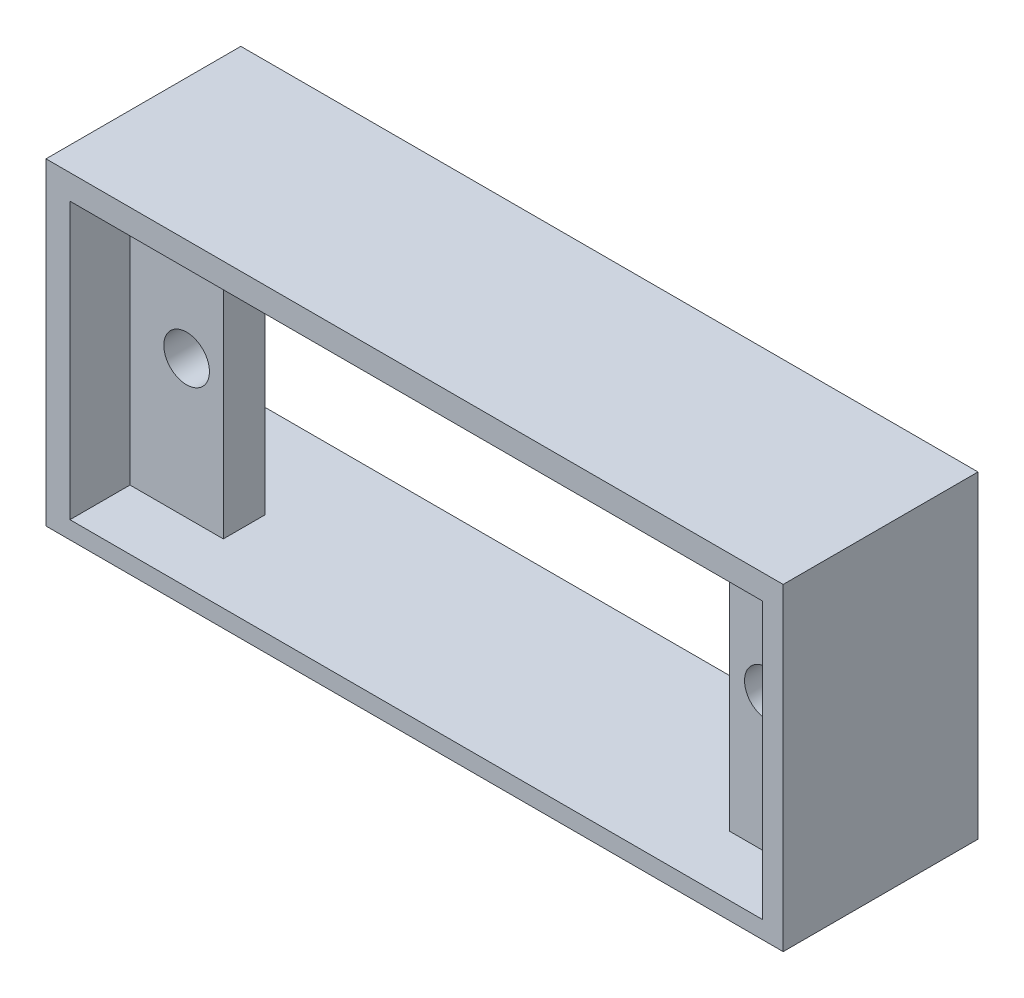
SolidWorks part; units mm, degrees
material "Custom Plastic"
ref_plane "Front Plane" through (0, 0, 0) normal (0, 0, 1) x (1, 0, 0)
ref_plane "Top Plane" through (0, 0, 0) normal (0, 1, 0) x (1, 0, 0)
ref_plane "Right Plane" through (0, 0, 0) normal (1, 0, 0) x (0, 0, -1)
sketch "Sketch1" plane through (0, 0, 0) normal (0, 0, 1) x (1, 0, 0)
  line L1 (0, 15) -> (145, 15)
  line L2 (0, 15) -> (0, -15)
  line L3 (0, -15) -> (145, -15)
  line L4 (145, 15) -> (145, -15)
  circle A0 centre (0, 0) radius 27.5
  circle A1 centre (145, 0) radius 27.5
  circle A2 centre (0, 0) radius 20
  point P9 (0, 0)
  dimension "D1" = 55
  dimension "D4" = 55
  dimension "D5" = 40
  dimension "D2" = 145
  dimension "D3" = 30
extrude "Boss-Extrude1" add sketch "Sketch1" along normal blind 25 contours L3 A1 L1 L4 | A1 L1 A0 L3 | L1 A1 L3 L4 | A2 L3 A0 L1 | A2 L1 A0 L3 | L3 A2 L1 L2 | L1 A2 L3 L2 region at (-6.7804, 0, 0) region at (9.0671, 0, 0) region at (-20.747, 0, 0) region at (21.8665, 0, 0) region at (72.5, 0, 0) region at (151.4116, 0, 0) region at (131.9332, 0, 0)
sketch "Sketch16" plane through (0, 0, 0) normal (0, 0, -1) x (-1, 0, 0)
  line L0 (-121.9511, -15) -> (-133.5193, -6.65) construction
  line L1 (-133.5193, -6.65) -> (-166.9193, -6.65)
  line L2 (-133.5193, -6.65) -> (-133.5193, 6.65)
  line L3 (-133.5193, 6.65) -> (-166.9193, 6.65)
  line L4 (-166.9193, -6.65) -> (-166.9193, 6.65)
  line L5 (-23.0489, -15) -> (-121.9511, -15) construction
  line L7 (-133.5193, 6.65) -> (-121.9511, 15) construction
  arc A1 (-121.9511, 15) -> (-121.9511, -15) centre (-145, 0) ccw construction
  dimension "D1" = 11.5682
  dimension "D2" = 33.4
  dimension "D3" = 13.3
extrude "Cut-Extrude10" cut sketch "Sketch16" against normal blind 4.5
ref_plane "Plane1" through (0, 0, 0) normal (0, -1, 0) x (-1, 0, 0)
sketch "Sketch19" plane through (0, 0, 0) normal (0, 0, -1) x (-1, 0, 0)
  circle A0 centre (0, 0) radius 20
extrude "Cut-Extrude14" cut sketch "Sketch19" against normal blind 5 contours A0
ref_plane "Plane2" through (0, 0, 6.5) normal (0, 0, -1) x (-1, 0, 0)
sketch "Sketch17" plane through (0, 0, 0) normal (0, 0, -1) x (-1, 0, 0)
  line L1 (-162.4193, 6.65) -> (-138.0193, 6.65)
  line L2 (-162.4193, 6.65) -> (-162.4193, -6.65)
  line L3 (-162.4193, -6.65) -> (-138.0193, -6.65)
  line L4 (-133.5193, -6.65) -> (-133.5193, 6.65)
  line L5 (-133.5193, 6.65) -> (-166.9193, 6.65)
  line L7 (-166.9193, -6.65) -> (-133.5193, -6.65)
  line L8 (-133.5193, -6.65) -> (-133.5193, 6.65)
  line L9 (-133.5193, 6.65) -> (-166.9193, 6.65)
  line L11 (-166.9193, -6.65) -> (-133.5193, -6.65)
  line L12 (-138.0193, 6.65) -> (-138.0193, -6.65)
  line L15 (-166.9193, 6.65) -> (-166.9193, -6.65)
  line L17 (-166.9193, 6.65) -> (-166.9193, -6.65)
  line M9 (-166.9193, 6.65) -> (-133.5193, 6.65)
  line M11 (-133.5193, -6.65) -> (-166.9193, -6.65)
  dimension "D2" = 4.5
  dimension "D3" = 4.5
  dimension "D1" = 0
extrude "Cut-Extrude11" cut sketch "Sketch17" against normal through all contours L12 L2 M9 M11 region at (150.2193, 0, 0)
sketch "Sketch18" plane through (0, 0, 0) normal (0, -1, 0) x (-1, 0, 0)
  line L0 (-138.0193, -25) -> (-138.0193, -15)
  line L6 (-122.0193, -25) -> (-122.0193, -22.5)
  line L8 (-166.9193, -4.5) -> (-162.4193, -4.5)
  line L9 (-166.9193, 0) -> (-166.9193, -4.5)
  line L11 (-166.9193, 0) -> (-166.9193, -4.5)
  line L13 (-133.5193, -4.5) -> (-133.5193, 0)
  line L14 (-133.5193, 0) -> (-166.9193, 0)
  line L16 (-166.9193, -4.5) -> (-162.4193, -4.5)
  line L21 (-133.5193, -4.5) -> (-133.5193, 0)
  line L22 (-133.5193, 0) -> (-166.9193, 0)
  line L26 (-122.0193, -22.5) -> (-138.0193, -15)
  line L28 (-23.0489, -25) -> (-121.9511, -25) construction
  line L30 (-138.0193, -25) -> (-122.0193, -25)
  line L31 (-138.0193, -15) -> (-138.0193, -25)
  line L34 (-162.4193, -25) -> (-138.0193, -25)
  line L35 (-162.4193, -25) -> (-138.0193, -25)
  line L36 (-138.0193, -25) -> (-138.0193, -4.5)
  line L37 (-138.0193, -25) -> (-138.0193, -4.5)
  line L38 (-162.4193, -4.5) -> (-162.4193, -25)
  line L40 (-162.4193, -4.5) -> (-162.4193, -25)
  line L42 (-138.0193, -4.5) -> (-133.5193, -4.5)
  line L43 (-138.0193, -4.5) -> (-133.5193, -4.5)
  dimension "D2" = 15
  dimension "D3" = 16
  dimension "D4" = 2.5
  dimension "D1" = 0
extrude "Cut-Extrude13" cut sketch "Sketch18" against normal mid plane 12.9 contours L0 region at (131.6193, 0, 21.5)
sketch "Sketch20" plane through (0, 0, 6.5) normal (0, 0, -1) x (-1, 0, 0)
  line L0 (-133.5193, 6.65) -> (-166.9193, 6.65) construction
  line L1 (-166.9193, 6.65) -> (-133.5193, 6.65)
  line L2 (-166.9193, 6.65) -> (-166.9193, -6.65)
  line L3 (-166.9193, -6.65) -> (-133.5193, -6.65)
  line L4 (-133.5193, 6.65) -> (-133.5193, -6.65)
  line L5 (-166.9193, 6.65) -> (-166.9193, -6.65) construction
  line L6 (-166.9193, -6.65) -> (-133.5193, -6.65) construction
  dimension "D1" = 33.4
extrude "Cut-Extrude15" cut sketch "Sketch20" against normal through all
sketch "Sketch21" plane through (0, 0, 0) normal (0, 0, -1) x (-1, 0, 0)
  circle A0 centre (-136.25, 0) radius 1.1
  circle A1 centre (-164.25, 0) radius 1.1
  dimension "D3" = 2.2
  dimension "D1" = 14.2989
  dimension "D2" = 28
extrude "Cut-Extrude16" cut sketch "Sketch21" against normal through all contours A1 | A0 region at (136.25, 0, 0) region at (164.25, 0, 0)
ref_axis "Axis1" through (136.25, 0, 34.2314) along (0, 0, -1)
sketch "Sketch22" plane through (0, 0, 25) normal (0, 0, 1) x (1, 0, 0)
  circle A0 centre (0, 0) radius 2
  arc A1 (23.0489, 15) -> (23.0489, -15) centre (0, 0) ccw construction
  dimension "D1" = 4
extrude "Cut-Extrude17" cut sketch "Sketch22" against normal up to surface (20 mm away) contours A0 region at (0, 0, 25) up to face at (-20, 0, 5)
ref_plane "Plane3" through (166.9193, -6.65, 0) normal (0, -1, 0) x (-1, 0, 0)
sketch "Sketch23" plane through (0, 0, 0) normal (0, 0, -1) x (-1, 0, 0)
  line L1 (-132.3633, 32.6117) -> (34.4982, 32.6117)
  line L2 (-132.3633, 32.6117) -> (-132.3633, -47.3537)
  line L3 (-132.3633, -47.3537) -> (34.4982, -47.3537)
  line L4 (34.4982, 32.6117) -> (34.4982, -47.3537)
  line L5 (-182.0639, 37.331) -> (-132.3633, 37.331)
  line L6 (-182.0639, 37.331) -> (-182.0639, 7.8406)
  line L7 (-182.0639, 7.8406) -> (-132.3633, 7.8406)
  line L8 (-132.3633, 37.331) -> (-132.3633, 7.8406)
  line L9 (-182.0639, -7.4938) -> (-132.3633, -7.4938)
  line L10 (-182.0639, -7.4938) -> (-182.0639, -47.3537)
  line L11 (-182.0639, -47.3537) -> (-132.3633, -47.3537)
  line L12 (-132.3633, -7.4938) -> (-132.3633, -47.3537)
  line L13 (-182.0639, 7.8406) -> (-167.9061, 7.8406)
  line L14 (-182.0639, 7.8406) -> (-182.0639, -7.4938)
  line L15 (-182.0639, -7.4938) -> (-167.9061, -7.4938)
  line L16 (-167.9061, 7.8406) -> (-167.9061, -7.4938)
  circle M17 centre (0, 0) radius 20
  arc M22 (-23.0489, -15) -> (-23.0489, 15) centre (0, 0) ccw
  line M23 (-23.0489, 15) -> (-121.9511, 15)
  arc M24 (-121.9511, 15) -> (-121.9511, -15) centre (-145, 0) ccw
  line M25 (-121.9511, -15) -> (-23.0489, -15)
extrude "Cut-Extrude18" cut sketch "Sketch23" against normal through all contours L8 L5 L6 L7 L2 M24 | L7 L14 L9 M24 | L10 L11 L2 L9 M24 | L4 L1 L2 L3 M24 M23 M22 M25 | L2 M24 M25 M22 M23 M17 | L9 L2 M24 | L16 L7 L9 M24 | L7 L2 M24 | M17 region at (48.9325, 30.7614, 0) region at (163.0327, 27.0393, 0) region at (60.4533, 0, 0) region at (149.2111, 16.4613, 0) region at (177.096, 0.1861, 0) region at (170.035, 0.1435, 0) region at (160.9237, -32.6311, 0) region at (149.2685, -16.2725, 0) region at (0, 0, 0)
sketch "Sketch24" plane through (132.3633, 0, 0) normal (-1, 0, 0) x (0, 0, 1)
  line L1 (9.3936, 10.2373) -> (27.4541, 10.2373)
  line L2 (9.3936, 10.2373) -> (9.3936, -13.4234)
  line L3 (9.3936, -13.4234) -> (27.4541, -13.4234)
  line L4 (27.4541, 10.2373) -> (27.4541, -13.4234)
extrude "Cut-Extrude19" cut sketch "Sketch24" against normal through all
